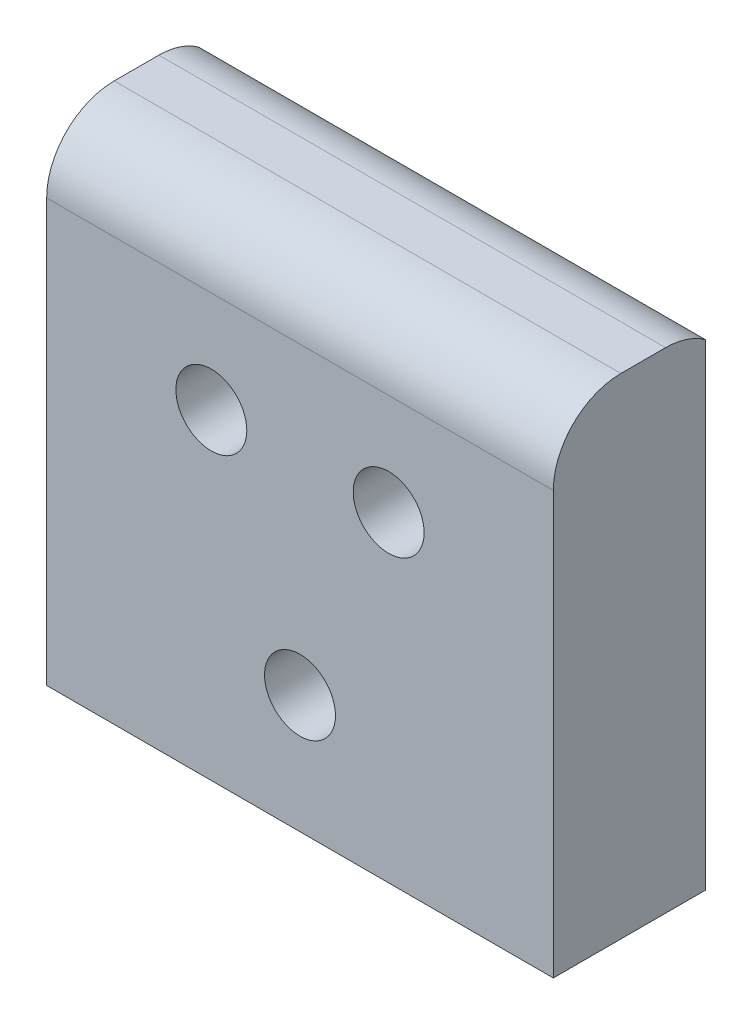
SolidWorks part; units mm, degrees
ref_plane "xy_plane" through (0, 0, 0) normal (0, 0, 1) x (1, 0, 0)
ref_plane "zx_plane" through (0, 0, 0) normal (0, 1, 0) x (1, 0, 0)
ref_plane "yz_plane" through (0, 0, 0) normal (1, 0, 0) x (0, 0, -1)
ref_axis "x_axis" through (-17.2546, 0, 0) along (1, 0, 0)
ref_axis "y_axis" through (0, -13.4069, 0) along (0, 1, 0)
ref_axis "z_axis" through (0, 0, -7.1068) along (0, 0, 1)
ref_plane "xMid_plane" through (0, 0, 0) normal (1, 0, 0) x (0, 0, -1)
ref_plane "xMin_plane" through (-15, 0, 0) normal (1, 0, 0) x (0, 0, -1)
ref_plane "xMax_plane" through (15, 0, 0) normal (1, 0, 0) x (0, 0, -1)
ref_plane "yMid_plane" through (0, 0, 0) normal (0, 1, 0) x (1, 0, 0)
ref_plane "yMin_plane" through (0, -14.5, 0) normal (0, 1, 0) x (1, 0, 0)
ref_plane "yMax_plane" through (0, 14.5, 0) normal (0, 1, 0) x (1, 0, 0)
ref_plane "zMid_plane" through (0, 0, 0) normal (0, 0, 1) x (1, 0, 0)
ref_plane "zMin_plane" through (0, 0, -4.5) normal (0, 0, 1) x (1, 0, 0)
ref_plane "zMax_plane" through (0, 0, 4.5) normal (0, 0, 1) x (1, 0, 0)
sketch "projectionX_sketch" plane through (0, 0, 0) normal (1, 0, 0) x (0, 0, -1)
  line L0 (9.6639, 14.5) -> (-9.6639, 14.5) construction
  line L1 (-0.5, 14.5) -> (2.1457, 14.5)
  line L2 (-4.5, 10.5) -> (-4.5, -14.5)
  line L3 (-4.5, -14.5) -> (4.5, -14.5)
  line L4 (4.5, 13.7338) -> (4.5, -14.5)
  line L5 (8.5433, -14.5) -> (-8.5433, -14.5) construction
  line L7 (2.1457, 10.5) -> (4.5, 13.7338) construction
  line L8 (4.5, 12.9932) -> (4.5, -12.9932) construction
  line L9 (-4.5, 12.6106) -> (-4.5, -12.6106) construction
  line L10 (0, -13.4069) -> (0, 13.7724) construction
  arc A0 (-0.5, 14.5) -> (-4.5, 10.5) centre (-0.5, 10.5) ccw
  arc A1 (2.1457, 14.5) -> (4.5, 13.7338) centre (2.1457, 10.5) cw
  dimension "D1" = 4
  dimension "D2" = 36.055
extrude "mainBody_extrude" add sketch "projectionX_sketch" along normal up to surface (15 mm away) from surface up to plane "xMax_plane" starting at plane "xMin_plane"
ref_plane "pivotTargetZ_plane" through (0, 0, -4.5) normal (0, 0, 1) x (1, 0, 0)
sketch "viseScrewsThreadedHoles_sketch" plane through (0, 0, 0) normal (0, 0, 1) x (1, 0, 0)
  circle A0 centre (-5.25, 4.5) radius 2.1
  circle A1 centre (5.25, 4.5) radius 2.1
  point P4 (0, 0)
  point P6 (0, 0)
  dimension "D1" = 4.2
extrude "viseScrewsThreadedHoles_cut" cut sketch "viseScrewsThreadedHoles_sketch" against normal through all both and the other way through all from surface starting at plane "zMid_plane"
sketch "threadedHoleForTerminalScrew_sketch" plane through (0, 0, 4.5) normal (0, 0, 1) x (1, 0, 0)
  circle A0 centre (0, -7.5) radius 2.1
  point P2 (0, 0)
  dimension "D1" = 4.2
extrude "Cut-Extrude2" cut sketch "threadedHoleForTerminalScrew_sketch" against normal through all both and the other way through all from surface starting at plane "zMid_plane"
equation "\"D1@xMin_plane\"= \"externalParameters.this.extent.x\" / 2"
equation "\"D1@xMax_plane\" = \"externalParameters.this.extent.x\" / 2"
equation "\"D1@yMin_plane\" = \"externalParameters.this.extent.y\" / 2"
equation "\"D1@yMax_plane\" = \"externalParameters.this.extent.y\" / 2"
equation "\"D1@zMin_plane\" = \"externalParameters.this.extent.z\" / 2"
equation "\"D1@zMax_plane\" = \"externalParameters.this.extent.z\" / 2"
equation "\"D1@viseScrewsThreadedHoles_sketch\"=\"externalParameters.arm.viseScrew.tappableHoleDiameter\""
equation "\"D1@threadedHoleForTerminalScrew_sketch\" = \"externalParameters.arm.terminalScrew.tappableHoleDiameter\""
